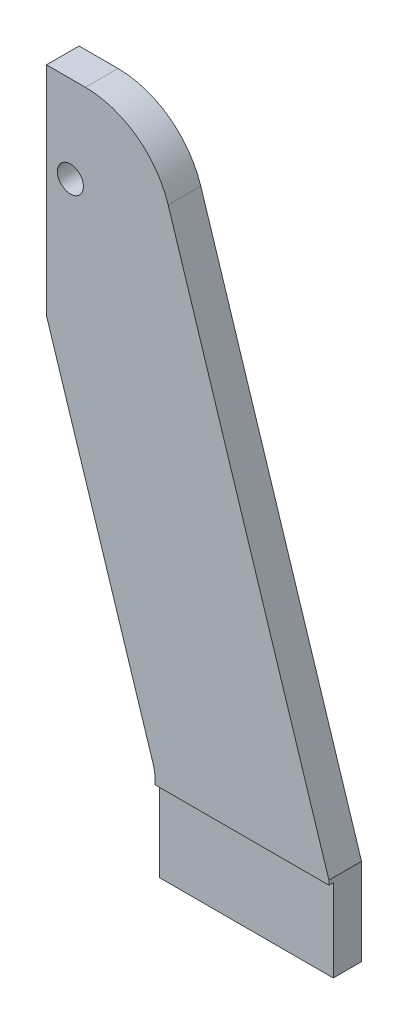
SolidWorks part; units mm, degrees
ref_plane "Alzado" through (0, 0, 0) normal (0, 0, 1) x (1, 0, 0)
ref_plane "Planta" through (0, 0, 0) normal (0, 1, 0) x (1, 0, 0)
ref_plane "Vista lateral" through (0, 0, 0) normal (1, 0, 0) x (0, 0, -1)
sketch "Croquis1" plane through (0, 0, 0) normal (0, 0, 1) x (1, 0, 0)
  line L0 (80, 0) -> (80, 40)
  line L1 (-50, 300) -> (-32.095, 300)
  line L2 (-50, 300) -> (-50, 200)
  line L3 (0, 0) -> (80, 0)
  line L4 (6.0164, 272.1459) -> (80, 40)
  line L9 (-50, 200) -> (-0.9443, 46.0729)
  line L11 (0, 40) -> (0, 0)
  arc A2 (6.0164, 272.1459) -> (-32.095, 300) centre (-32.095, 260) ccw
  arc A3 (-0.9443, 46.0729) -> (0, 40) centre (-20, 40) cw
  dimension "D7" = 40
  dimension "D9" = 40
  dimension "D4" = 20
  dimension "D1" = 50
  dimension "D2" = 300
  dimension "D3" = 80
  dimension "D5" = 100
  dimension "D6" = 40
extrude "Saliente-Extruir1" add sketch "Croquis1" along normal blind 15
sketch "Croquis2" plane through (0, 0, 0) normal (0, 0, -1) x (-1, 0, 0)
  line L0 (32.095, 300) -> (50, 300) construction
  line L2 (50, 300) -> (50, 200) construction
  circle A0 centre (39, 260) radius 6
  dimension "D3" = 12
  dimension "D1" = 40
  dimension "D2" = 11
extrude "Cortar-Extruir1" cut sketch "Croquis2" against normal through all
hole_wizard "Perforador para roscar para macho de roscar para M44" positions "Croquis7" profile "Croquis8" hole size "M4" standard "DIN"
sketch "Croquis7" plane through (0, 0, 0) normal (0, 0, -1) x (-1, 0, 0)
  line L0 (39, 278.25) -> (39, 241.75)
  circle A0 centre (39, 260) radius 6 construction
  point P10 (39, 278.25)
  point P12 (39, 241.75)
  dimension "D1" = 18.25
  dimension "D2" = 18.25
sketch "Croquis8" plane through (-39, 241.75, 0) normal (1, 0, 0) x (0, 1, 0)
  line L0 (0, 0) -> (0, 7.9914)
  line L1 (0, 7.9914) -> (1.65, 7)
  line L2 (1.65, 7) -> (1.65, 0)
  line L5 (1.65, 0) -> (0, 0)
  line L10 (0, 7.9914) -> (-1.65, 7) construction
  line L11 (0, -6.35) -> (0, 107.95) construction
  dimension "Diámetro de taladro" = 3.3
  dimension "Profundidad de taladro" = 7
  dimension "Ángulo de perforador" = 118
sketch "Croquis9" plane through (0, 0, 15) normal (0, 0, 1) x (1, 0, 0)
  line L1 (0, 0) -> (80, 0)
  line L2 (0, 0) -> (0, 38)
  line L3 (0, 38) -> (80, 38)
  line L4 (80, 0) -> (80, 38)
  dimension "D1" = 80
  dimension "D2" = 38
extrude "Cortar-Extruir2" cut sketch "Croquis9" against normal blind 2
hole_wizard "Taladros de espiga de Ø4.0mm1" positions "Croquis10" profile "Croquis12" hole size "Ø4.0" standard "DIN"
sketch "Croquis10" plane through (-50, 0, 0) normal (-1, 0, 0) x (0, 0, 1)
  line L0 (0, 300) -> (0, 200) construction
  line L1 (15, 300) -> (0, 300) construction
  point P0 (6, 274)
  point P2 (6, 246)
  dimension "D1" = 6
  dimension "D2" = 6
  dimension "D3" = 26
  dimension "D4" = 54
sketch "Croquis12" plane through (-50, 274, 6) normal (0, 1, 0) x (0, 0, 1)
  line L0 (0, 0) -> (0, 18.2017)
  line L1 (0, 18.2017) -> (2, 17)
  line L2 (2, 17) -> (2, 0)
  line L5 (2, 0) -> (0, 0)
  line L10 (0, 18.2017) -> (-2, 17) construction
  line L11 (0, -6.35) -> (0, 107.95) construction
  dimension "Diámetro de taladro" = 4
  dimension "Profundidad de taladro" = 17
  dimension "Ángulo de perforador" = 118
hole_wizard "Taladro roscado M41" positions "Croquis13" profile "Croquis14" tap size "M4" standard "DIN"
sketch "Croquis13" plane through (-50, 0, 0) normal (-1, 0, 0) x (0, 0, 1)
  line L0 (0, 300) -> (0, 200) construction
  line L1 (15, 300) -> (0, 300) construction
  point P0 (6, 285)
  point P2 (6, 235)
  dimension "D1" = 6
  dimension "D2" = 6
  dimension "D3" = 15
  dimension "D4" = 65
sketch "Croquis14" plane through (-50, 285, 6) normal (0, 1, 0) x (0, 0, 1)
  line L0 (0, 0) -> (0, 12.4914)
  line L1 (0, 12.4914) -> (1.65, 11.5)
  line L2 (1.65, 11.5) -> (1.65, 0)
  line L5 (1.65, 0) -> (0, 0)
  line L10 (0, 12.4914) -> (-1.65, 11.5) construction
  line L11 (0, -6.35) -> (0, 107.95) construction
  dimension "Diámetro de perforador para roscar" = 3.3
  dimension "Profundidad de perforador para roscar" = 11.5
  dimension "Ángulo de perforador" = 118
cosmetic thread "Rosca de taladro1" parameters "D1"=8, "D2"=4
cosmetic thread "Rosca de taladro2" parameters "D1"=8, "D2"=4
